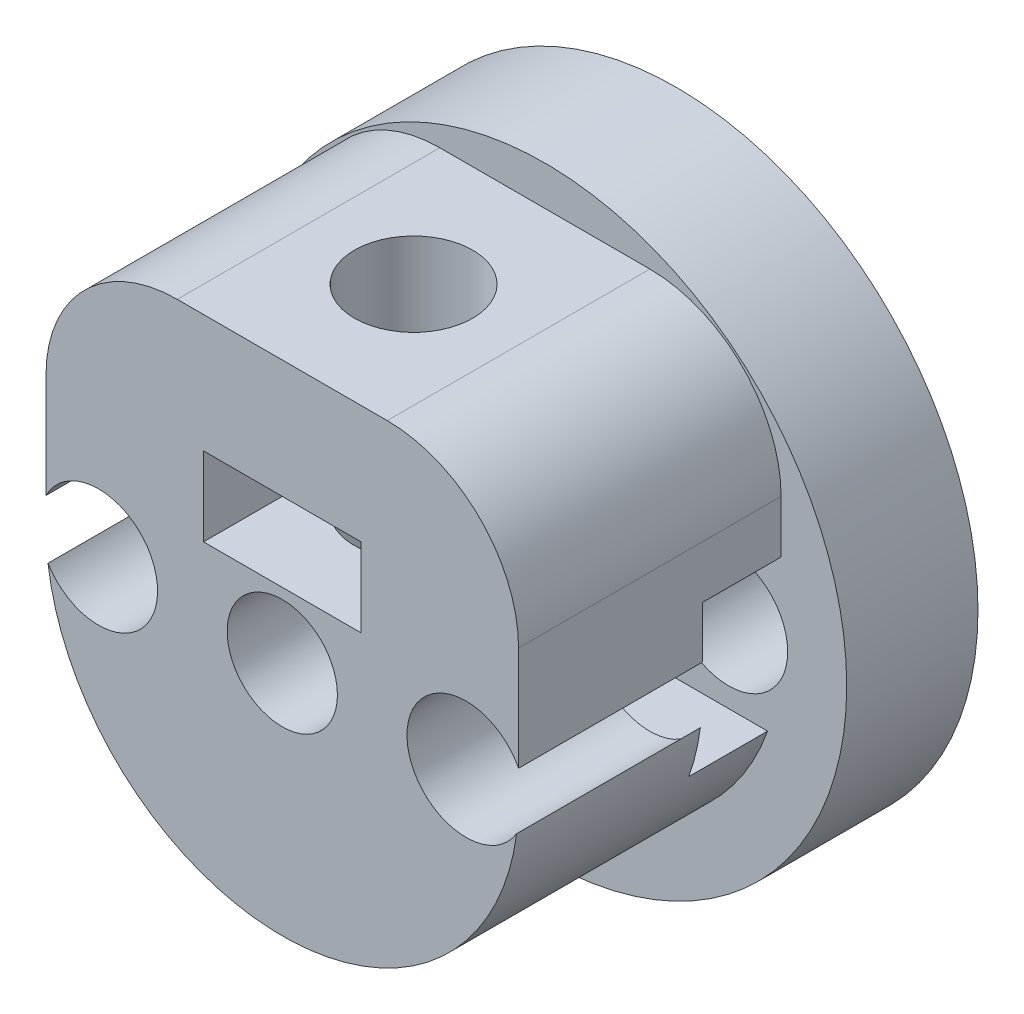
SolidWorks part; units mm, degrees
ref_plane "Front Plane" through (0, 0, 0) normal (0, 0, 1) x (1, 0, 0)
ref_plane "Top Plane" through (0, 0, 0) normal (0, 1, 0) x (1, 0, 0)
ref_plane "Right Plane" through (0, 0, 0) normal (1, 0, 0) x (0, 0, -1)
sketch "Sketch1" plane through (0, 0, 0) normal (0, 0, 1) x (1, 0, 0)
  circle A0 centre (0, 0) radius 11.5
  dimension "D1" = 23
extrude "Boss-Extrude1" add sketch "Sketch1" along normal blind 5
sketch "Sketch2" plane through (0, 0, 5) normal (0, 0, 1) x (1, 0, 0)
  line L0 (0, 0) -> (0, 7) construction
  circle A0 centre (0, 7) radius 2.25
  dimension "D2" = 4.5
  dimension "D1" = 7
extrude "Cut-Extrude1" cut sketch "Sketch2" against normal through all
pattern_circular "CirPattern1" count 4 over 360 about axis through (0, 0, 5) along (0, 0, 1) of "Cut-Extrude1"
sketch "Sketch3" plane through (0, 0, 5) normal (0, 0, 1) x (1, 0, 0)
  circle A0 centre (0, 0) radius 9
  dimension "D1" = 18
extrude "Boss-Extrude2" add sketch "Sketch3" along normal blind 10
sketch "Sketch4" plane through (0, 0, 15) normal (0, 0, 1) x (1, 0, 0)
  circle A0 centre (0, 0) radius 2.1
  dimension "D1" = 4.2
extrude "Cut-Extrude2" cut sketch "Sketch4" against normal through all
ref_plane "Plane1" through (0, 10, 0) normal (0, 1, 0) x (1, 0, 0)
sketch "Sketch5" plane through (0, 10, 0) normal (0, 1, 0) x (1, 0, 0)
  line L0 (-9, -5) -> (-9, -15) construction
  line L1 (-9, -5) -> (9, -5)
  line L2 (-9, -5) -> (-9, -15)
  line L3 (-9, -15) -> (9, -15)
  line L4 (9, -5) -> (9, -15)
  line L5 (9, -15) -> (9, -5) construction
  line L7 (-11.5, -5) -> (11.5, -5) construction
  line L8 (9, -15) -> (9, -5) construction
extrude "Boss-Extrude3" add sketch "Sketch5" against normal up to next
sketch "Sketch6" plane through (0, 10, 0) normal (0, 1, 0) x (1, 0, 0)
  line L0 (-9, -10) -> (9, -10) construction
  line L1 (-9, -5) -> (-9, -15) construction
  line L2 (9, -15) -> (9, -5) construction
  circle A0 centre (0, -10) radius 2.25
  dimension "D1" = 4.5
extrude "Cut-Extrude3" cut sketch "Sketch6" against normal blind 10
chamfer "Chamfer2" distance 1 angle 45 4 edges at (-2.25, -7, 0) (-7, 2.25, 0) (7, -2.25, 0) (2.25, 7, 0)
fillet "Fillet1" radius 5 2 edges at (9, 10, 10) (-9, 10, 10)
sketch "Sketch7" plane through (0, 0, 5) normal (0, 0, -1) x (-1, 0, 0)
  line L1 (-9, 1.0308) -> (-9, 0)
  line L2 (-9, 1.0308) -> (-9, 0)
  line L3 (9, 0) -> (9, 1.0308)
  line L4 (9, 0) -> (9, 1.0308)
  arc A2 (-8.9241, -1.1663) -> (-9, 1.0308) centre (-7, 0) ccw
  arc A3 (-9, 0) -> (-8.9241, -1.1663) centre (0, 0) ccw
  arc A4 (-8.9241, -1.1663) -> (-9, 1.0308) centre (-7, 0) ccw
  arc A5 (-9, 0) -> (-8.9241, -1.1663) centre (0, 0) ccw
  arc A6 (9, 1.0308) -> (8.9241, -1.1663) centre (7, 0) ccw
  arc A7 (8.9241, -1.1663) -> (9, 0) centre (0, 0) ccw
  arc A8 (9, 1.0308) -> (8.9241, -1.1663) centre (7, 0) ccw
  arc A9 (8.9241, -1.1663) -> (9, 0) centre (0, 0) ccw
  dimension "D1" = 0
  dimension "D2" = 0
extrude "Cut-Extrude4" cut sketch "Sketch7" against normal through all
sketch "Sketch8" plane through (0, 0, 15) normal (0, 0, 1) x (1, 0, 0)
  line L0 (0, 4) -> (0, 0) construction
  line L1 (-3, 5.5) -> (3, 5.5)
  line L2 (-3, 5.5) -> (-3, 2.5)
  line L3 (-3, 2.5) -> (3, 2.5)
  line L4 (3, 5.5) -> (3, 2.5)
  line L5 (-3, 5.5) -> (3, 2.5) construction
  line L6 (-3, 2.5) -> (3, 5.5) construction
  point P0 (0, 4)
  dimension "D1" = 6
  dimension "D2" = 3
  dimension "D3" = 4
extrude "Cut-Extrude7" cut sketch "Sketch8" against normal blind 10
sketch "Sketch9" plane through (9, 0, 0) normal (1, 0, 0) x (0, 0, -1)
  line L0 (-5, 11.5) -> (-5, -11.5) construction
  line L1 (-5, 3) -> (-8, 3)
  line L2 (-5, 3) -> (-5, -3)
  line L3 (-5, -3) -> (-8, -3)
  line L4 (-8, 3) -> (-8, -3)
  line L5 (-5, 0) -> (0, 0) construction
  line L6 (0, -11.5) -> (0, 11.5) construction
  dimension "D1" = 6
  dimension "D2" = 3
extrude "Cut-Extrude8" cut sketch "Sketch9" against normal blind 6
mirror "Mirror1" about plane through (0, 0, 0) normal (1, 0, 0) of "Cut-Extrude8"
